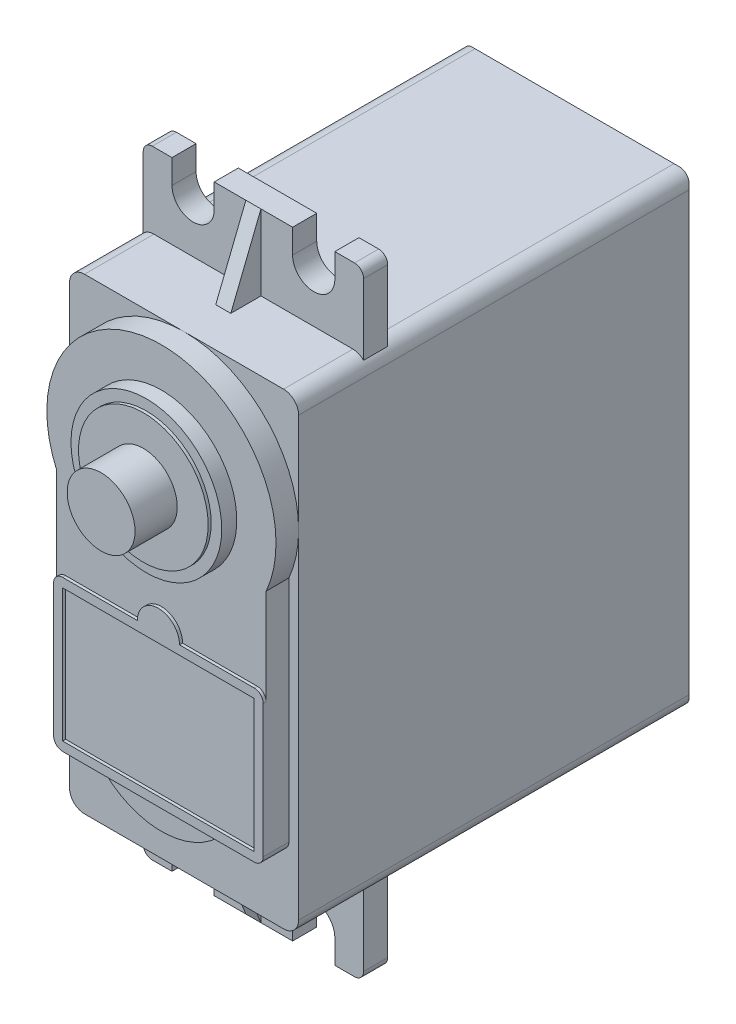
SolidWorks part; units mm, degrees
ref_plane "Front Plane" through (0, 0, 0) normal (0, 0, 1) x (1, 0, 0)
ref_plane "Top Plane" through (0, 0, 0) normal (0, 1, 0) x (1, 0, 0)
ref_plane "Right Plane" through (0, 0, 0) normal (1, 0, 0) x (0, 0, -1)
sketch "Sketch1" plane through (0, 0, 0) normal (1, 0, 0) x (0, 0, -1)
  line L1 (17.7165, 19.685) -> (-17.7165, 19.685)
  line L2 (17.7165, 19.685) -> (17.7165, -19.685)
  line L3 (17.7165, -19.685) -> (-17.7165, -19.685)
  line L4 (-17.7165, 19.685) -> (-17.7165, -19.685)
  line L5 (17.7165, 19.685) -> (-17.7165, -19.685) construction
  line L6 (17.7165, -19.685) -> (-17.7165, 19.685) construction
  point P0 (0, 0)
  dimension "D1" = 35.433
  dimension "D2" = 39.37
extrude "Boss-Extrude1" add sketch "Sketch1" along normal mid plane 19.304
sketch "Sketch2" plane through (0, 0, 17.7165) normal (0, 0, 1) x (1, 0, 0)
  line L2 (9.652, 19.685) -> (-9.652, 19.685) construction
  line L3 (9.652, 19.685) -> (9.652, -19.685) construction
  line L4 (-9.652, 19.685) -> (-9.652, -19.685) construction
  line L5 (-8.8265, 6.1274) -> (-8.8265, -13.8938)
  line L6 (-8.8265, -13.8938) -> (-4.7625, -13.8938)
  line L7 (8.8265, 6.1274) -> (8.8265, -13.8938)
  line L8 (8.8265, -13.8938) -> (4.7625, -13.8938)
  line L9 (9.652, -19.685) -> (-9.652, -19.685) construction
  arc A0 (-8.8265, 6.1274) -> (8.8265, 6.1274) centre (0, 10.033) cw
  arc A1 (-4.7625, -13.8938) -> (4.7625, -13.8938) centre (0, -8.9592) ccw
  dimension "D3" = 4.064
  dimension "D4" = 6.858
  dimension "D1" = 17.653
  dimension "D2" = 5.7912
extrude "Boss-Extrude2" add sketch "Sketch2" along normal blind 1.905
sketch "Sketch3" plane through (0, 0, 19.6215) normal (0, 0, 1) x (1, 0, 0)
  circle A0 centre (0, 10.033) radius 6.35
  dimension "D1" = 12.7
extrude "Boss-Extrude3" add sketch "Sketch3" along normal blind 1.27
sketch "Sketch4" plane through (0, 0, 20.8915) normal (0, 0, 1) x (1, 0, 0)
  circle A0 centre (0, 10.033) radius 5.461
  dimension "D1" = 10.922
extrude "Boss-Extrude4" add sketch "Sketch4" along normal blind 0.254
sketch "Sketch6" plane through (0, 0, 21.1455) normal (0, 0, 1) x (1, 0, 0)
  circle A0 centre (0, 10.033) radius 2.8575
  dimension "D1" = 5.715
extrude "Boss-Extrude5" add sketch "Sketch6" along normal blind 3.556
fillet "Fillet1" radius 0.762 2 edges at (8.8265, -13.8938, 18.669) (-8.8265, -13.8938, 18.669)
sketch "Sketch7" plane through (0, 0, 19.6215) normal (0, 0, 1) x (1, 0, 0)
  line L0 (8.8265, -13.1318) -> (8.8265, 6.1274) construction
  line L2 (-8.8265, 6.1274) -> (-8.8265, -13.1318) construction
  line L4 (8.8265, -13.1318) -> (8.8265, -1.9558)
  line L5 (-8.0645, -13.8938) -> (8.0645, -13.8938)
  line L6 (-8.8265, -1.9558) -> (-8.8265, -13.1318)
  line L7 (-8.0645, -1.1938) -> (-1.778, -1.1938)
  line L8 (1.778, -1.1938) -> (8.0645, -1.1938)
  line L9 (-8.0645, -1.9558) -> (-8.0645, -13.1318)
  line L10 (-8.0645, -13.1318) -> (8.0645, -13.1318)
  line L11 (8.0645, -13.1318) -> (8.0645, -1.9558)
  line L12 (8.0645, -1.9558) -> (-8.0645, -1.9558)
  arc A0 (8.0645, -13.8938) -> (8.8265, -13.1318) centre (8.0645, -13.1318) ccw construction
  arc A2 (-8.8265, -13.1318) -> (-8.0645, -13.8938) centre (-8.0645, -13.1318) ccw construction
  arc A3 (8.0645, -13.8938) -> (8.8265, -13.1318) centre (8.0645, -13.1318) ccw
  arc A4 (8.8265, -1.9558) -> (8.0645, -1.1938) centre (8.0645, -1.9558) ccw
  arc A5 (-8.8265, -13.1318) -> (-8.0645, -13.8938) centre (-8.0645, -13.1318) ccw
  arc A6 (-8.8265, -1.9558) -> (-8.0645, -1.1938) centre (-8.0645, -1.9558) cw
  arc A7 (1.778, -1.1938) -> (-1.778, -1.1938) centre (0, -1.1938) ccw
  dimension "D1" = 0.762
  dimension "D3" = 1.778
  dimension "D2" = 12.7
extrude "Boss-Extrude6" add sketch "Sketch7" along normal blind 0.254
chamfer "Chamfer1" distance 2.54 angle 45 4 edges at (0, -19.685, -17.7165) (-9.652, 0, -17.7165) (0, 19.685, -17.7165) (9.652, 0, -17.7165)
fillet "Fillet3" radius 1.27 2 edges at (9.652, 19.685, 1.27) (8.382, 18.415, -16.4465)
fillet "Fillet4" radius 1.27 6 edges at (-9.652, 19.685, 1.27) (-8.382, 18.415, -16.4465) (-9.652, -19.685, 1.27) (-8.382, -18.415, -16.4465) (9.652, -19.685, 1.27) (8.382, -18.415, -16.4465)
sketch "Sketch9" plane through (0, 0, -17.7165) normal (0, 0, -1) x (-1, 0, 0)
  line L1 (-9.652, -18.415) -> (-9.652, 18.415) construction
  line L3 (-8.382, 19.685) -> (8.382, 19.685) construction
  line L4 (6.214, 17.145) -> (-6.214, 17.145) construction
  line L5 (-7.112, 16.247) -> (-7.112, -16.247) construction
  line L6 (-5.1818, 17.145) -> (-5.1818, 19.685)
  line L7 (-7.112, 15.748) -> (-9.652, 15.748)
  line L8 (-9.652, 15.748) -> (-9.652, 19.685)
  line L9 (-5.1818, 19.685) -> (-9.652, 19.685)
  arc A0 (-5.1818, 17.145) -> (-7.112, 15.748) centre (-7.112, 17.78) cw
  dimension "D1" = 2.032
  dimension "D2" = 17.78
extrude "Cut-Extrude1" cut sketch "Sketch9" against normal blind 2.032
mirror "Mirror1" about plane through (0, 0, 0) normal (0, 1, 0) of "Cut-Extrude1"
mirror "Mirror2" about plane through (0, 0, 0) normal (1, 0, 0) of "Mirror1"
ref_plane "Plane1" through (0, 0, 11.8745) normal (0, 0, 1) x (1, 0, 0)
sketch "Sketch13" plane through (0, 0, 11.8745) normal (0, 0, 1) x (1, 0, 0)
  line L0 (-9.28, -19.313) -> (-9.28, -25.273)
  line L1 (-8.518, -26.035) -> (-6.858, -26.035)
  line L2 (9.28, -25.273) -> (9.28, -19.313)
  line L3 (8.382, -19.685) -> (-8.382, -19.685) construction
  line L4 (-3.302, -26.035) -> (3.302, -26.035)
  line L5 (6.858, -26.035) -> (8.518, -26.035)
  line L6 (-6.858, -26.035) -> (-6.858, -24)
  line L7 (-3.302, -26.035) -> (-3.302, -24)
  line L8 (3.302, -26.035) -> (3.302, -24)
  line L9 (6.858, -26.035) -> (6.858, -24)
  line L11 (8.382, -19.685) -> (-8.382, -19.685)
  arc A0 (-9.652, -18.415) -> (-8.382, -19.685) centre (-8.382, -18.415) ccw construction
  arc A1 (8.382, -19.685) -> (9.652, -18.415) centre (8.382, -18.415) ccw construction
  arc A2 (-6.858, -24) -> (-3.302, -24) centre (-5.08, -24) cw
  arc A3 (3.302, -24) -> (6.858, -24) centre (5.08, -24) cw
  arc A4 (9.28, -25.273) -> (8.518, -26.035) centre (8.518, -25.273) cw
  arc A5 (-8.518, -26.035) -> (-9.28, -25.273) centre (-8.518, -25.273) cw
  arc A8 (8.382, -19.685) -> (9.28, -19.313) centre (8.382, -18.415) ccw
  arc A9 (-9.28, -19.313) -> (-8.382, -19.685) centre (-8.382, -18.415) ccw
  dimension "D3" = 3.556
  dimension "D5" = 0.762
  dimension "D1" = 6.35
  dimension "D2" = 10.16
  dimension "D4" = 24
extrude "Boss-Extrude7" add sketch "Sketch13" against normal blind 2.032
sketch "Sketch14" plane through (0, 0, 0) normal (1, 0, 0) x (0, 0, -1)
  line L0 (-11.8745, -26.035) -> (-14.4145, -19.685)
  line L1 (-11.8745, -19.685) -> (-17.7165, -19.685) construction
  line L2 (-11.8745, -25.273) -> (-11.8745, -19.313) construction
  line L3 (-14.4145, -19.685) -> (-11.8745, -19.685)
  line L4 (-11.8745, -19.685) -> (-11.8745, -26.035)
  dimension "D1" = 2.54
extrude "Boss-Extrude8" add sketch "Sketch14" along normal mid plane 1.27
mirror "Mirror3" about plane through (0, 0, 0) normal (0, 1, 0) of "Boss-Extrude8", "Boss-Extrude7"
sketch "Sketch15" plane through (0, 0, 19.6215) normal (0, 0, 1) x (1, 0, 0)
  line L0 (46.5787, 96.1524) -> (267.9121, 96.1524) construction
